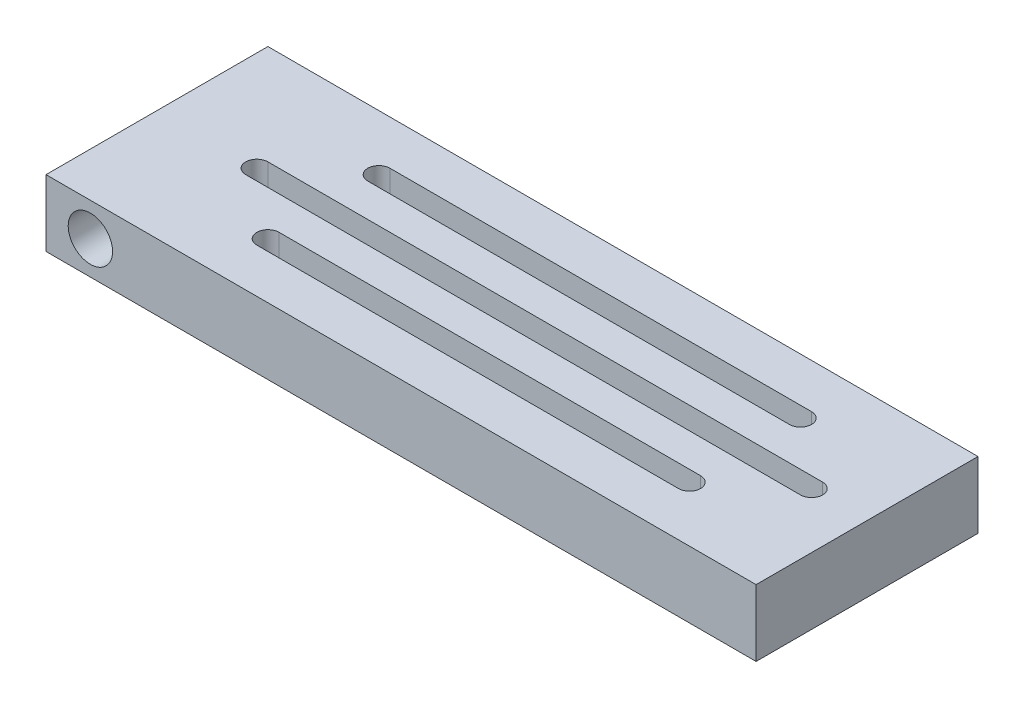
SolidWorks part; units mm, degrees
ref_plane "Front" through (0, 0, 0) normal (0, 0, 1) x (1, 0, 0)
ref_plane "Top" through (0, 0, 0) normal (0, 1, 0) x (1, 0, 0)
ref_plane "Right" through (0, 0, 0) normal (1, 0, 0) x (0, 0, -1)
sketch "Sketch1" plane through (0, 0, 0) normal (0, 1, 0) x (1, 0, 0)
  line L1 (-101.6, -31.75) -> (101.6, -31.75)
  line L2 (-101.6, -31.75) -> (-101.6, 31.75)
  line L3 (-101.6, 31.75) -> (101.6, 31.75)
  line L4 (101.6, -31.75) -> (101.6, 31.75)
  line L5 (-101.6, -31.75) -> (101.6, 31.75) construction
  line L6 (-101.6, 31.75) -> (101.6, -31.75) construction
  point P0 (0, 0)
  dimension "D1" = 203.2
  dimension "D2" = 63.5
extrude "Boss-Extrude1" add sketch "Sketch1" along normal mid plane 19.05 contours L3 L4 L1 L2
sketch "Sketch2" plane through (0, 9.525, 0) normal (0, 1, 0) x (1, 0, 0)
  line L0 (-73.025, 0) -> (85.725, 0) construction
  line L1 (-50, 0) -> (50, 0) construction
  line L2 (-73.025, 3.175) -> (85.725, 3.175)
  line L3 (-73.025, -3.175) -> (85.725, -3.175)
  line L4 (-53.975, 15.875) -> (66.675, 15.875) construction
  line L5 (-53.975, 19.05) -> (66.675, 19.05)
  line L6 (-53.975, 12.7) -> (66.675, 12.7)
  line L7 (-53.975, -15.875) -> (66.675, -15.875) construction
  line L8 (-53.975, -12.7) -> (66.675, -12.7)
  line L9 (-53.975, -19.05) -> (66.675, -19.05)
  line L10 (101.6, -31.75) -> (101.6, 31.75) construction
  arc A0 (-73.025, 3.175) -> (-73.025, -3.175) centre (-73.025, 0) ccw
  arc A1 (85.725, -3.175) -> (85.725, 3.175) centre (85.725, 0) ccw
  arc A2 (-53.975, 19.05) -> (-53.975, 12.7) centre (-53.975, 15.875) ccw
  arc A3 (66.675, 12.7) -> (66.675, 19.05) centre (66.675, 15.875) ccw
  arc A4 (-53.975, -12.7) -> (-53.975, -19.05) centre (-53.975, -15.875) ccw
  arc A5 (66.675, -19.05) -> (66.675, -12.7) centre (66.675, -15.875) ccw
  point P5 (6.35, 0)
  point P12 (6.35, 15.875)
  point P17 (6.35, -15.875)
  point P27 (88.9, 0)
  point P28 (69.85, 15.875)
  dimension "D1" = 6.35
  dimension "D2" = 6.35
  dimension "D3" = 158.75
  dimension "D4" = 12.7
  dimension "D5" = 120.65
  dimension "D6" = 9.525
  dimension "D7" = 9.525
extrude "Cut-Extrude1" cut sketch "Sketch2" against normal through all
sketch "Sketch3" plane through (0, 0, -31.75) normal (0, 0, -1) x (-1, 0, 0)
  line L0 (50, 0) -> (-50, 0) construction
  line L1 (101.6, 9.525) -> (101.6, -9.525) construction
  circle A0 centre (88.9, 0) radius 6.35
  point P2 (0, 0)
  dimension "D1" = 12.7
  dimension "D2" = 12.7
extrude "Cut-Extrude2" cut sketch "Sketch3" against normal up to next
